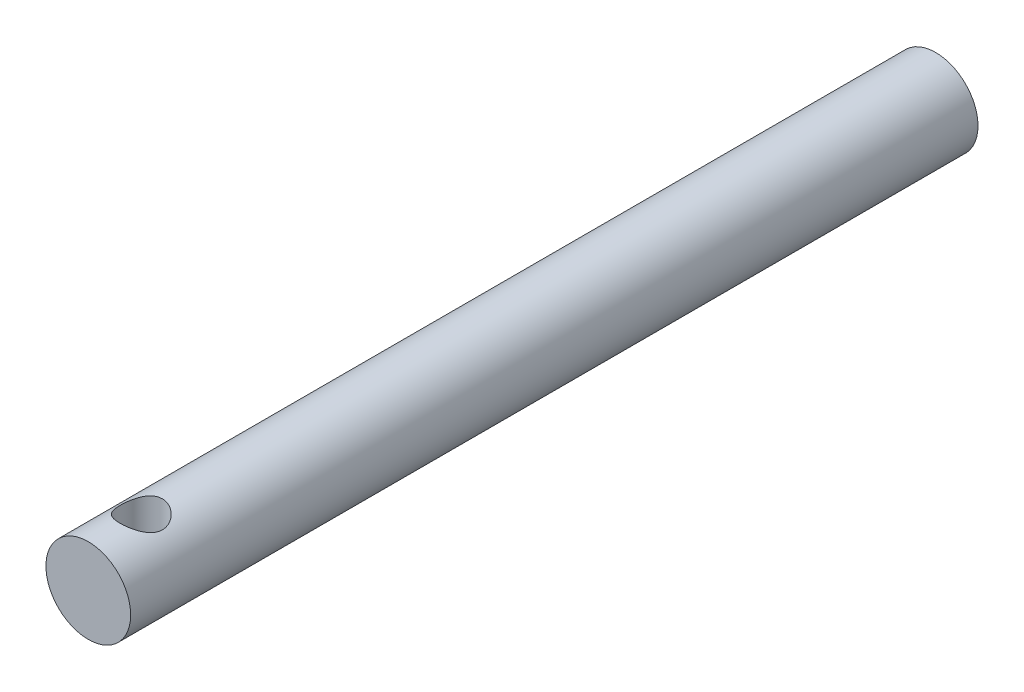
SolidWorks part; units mm, degrees
material "普通碳钢"
ref_plane "前视基准面" through (0, 0, 0) normal (0, 0, 1) x (1, 0, 0)
ref_plane "上视基准面" through (0, 0, 0) normal (0, 1, 0) x (1, 0, 0)
ref_plane "右视基准面" through (0, 0, 0) normal (1, 0, 0) x (0, 0, -1)
sketch "草图1" plane through (0, 0, 0) normal (0, 0, 1) x (1, 0, 0)
  circle A0 centre (0, 0) radius 8
  dimension "D1" = 16
extrude "凸台-拉伸1" add sketch "草图1" along normal blind 160
sketch "草图2" plane through (0, 0, 0) normal (0, 1, 0) x (1, 0, 0)
  line L0 (0, -136.9825) -> (0, -79.026) construction
  line L1 (-8, -160) -> (8, -160) construction
  circle A0 centre (0, -150) radius 4
  dimension "D1" = 8
  dimension "D2" = 10
extrude "切除-拉伸1" cut sketch "草图2" against normal blind 120 and the other way blind 120
sketch "草图3" plane through (0, 0, 0) normal (0, 0, -1) x (-1, 0, 0)
  circle A0 centre (0, 0) radius 4
  dimension "D1" = 8
extrude "切除-拉伸2" cut sketch "草图3" against normal blind 10
